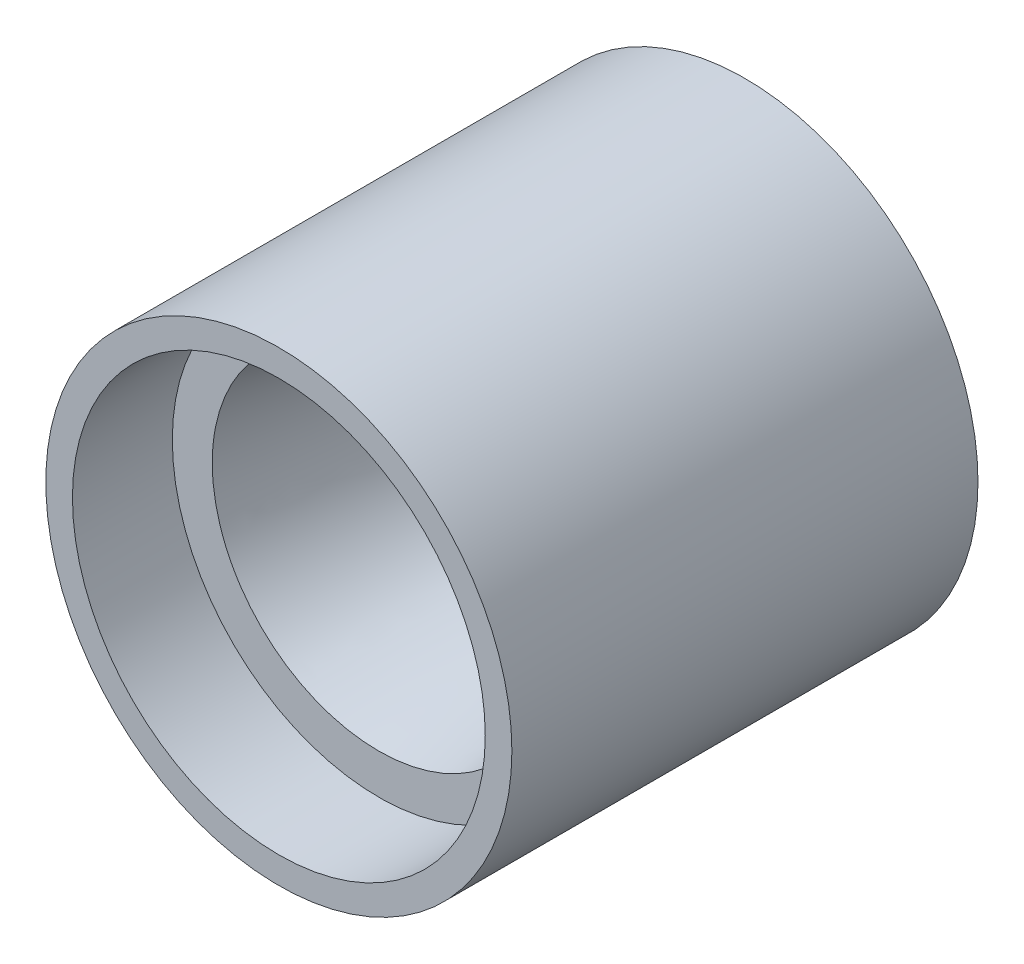
SolidWorks part; units mm, degrees
material "AISI 304"
ref_plane "Alzado" through (0, 0, 0) normal (0, 0, 1) x (1, 0, 0)
ref_plane "Planta" through (0, 0, 0) normal (0, 1, 0) x (1, 0, 0)
ref_plane "Vista lateral" through (0, 0, 0) normal (1, 0, 0) x (0, 0, -1)
sketch "Croquis1" plane through (0, 0, 0) normal (0, 0, 1) x (1, 0, 0)
  circle A0 centre (0, 0) radius 35
  circle A1 centre (0, 0) radius 31
extrude "Saliente-Extruir1" add sketch "Croquis1" along normal blind 70
sketch "Croquis2" plane through (0, 0, 0) normal (0, 0, -1) x (-1, 0, 0)
  circle A0 centre (0, 0) radius 31
extrude "Saliente-Extruir2" add sketch "Croquis2" against normal blind 55
sketch "Croquis3" plane through (0, 0, 55) normal (0, 0, 1) x (1, 0, 0)
  circle A0 centre (0, 0) radius 25
sketch "Croquis5" plane through (0, 0, 0) normal (0, 0, -1) x (-1, 0, 0)
  circle A0 centre (0, 0) radius 19.05
  point P3 (0, 0)
loft "Cortar-Recubrir2" cut profiles "Croquis3", "Croquis5" connector at (24.5057, 4.9466, 55) connector at (10.5288, 15.876, 0)
